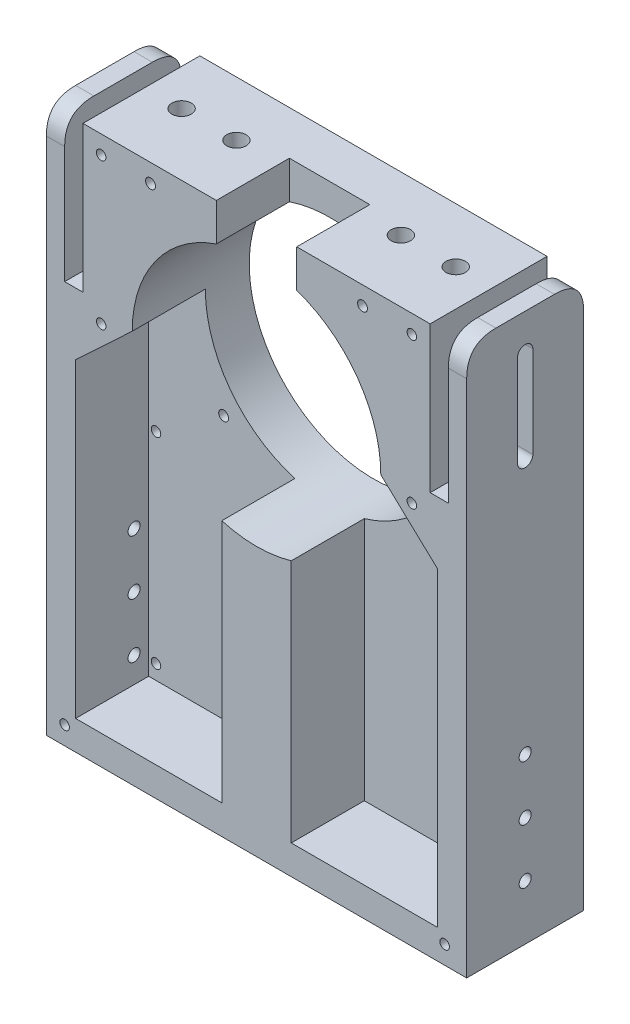
SolidWorks part; units mm, degrees
ref_plane "前基準面" through (0, 0, 0) normal (0, 0, 1) x (1, 0, 0)
ref_plane "上基準面" through (0, 0, 0) normal (0, 1, 0) x (1, 0, 0)
ref_plane "右基準面" through (0, 0, 0) normal (1, 0, 0) x (0, 0, -1)
sketch "草圖1" plane through (0, 0, 0) normal (0, 0, 1) x (1, 0, 0)
  line L1 (-57.5, -75) -> (57.5, -75)
  line L2 (-57.5, -75) -> (-57.5, 75)
  line L3 (-57.5, 75) -> (57.5, 75)
  line L4 (57.5, -75) -> (57.5, 75)
  line L5 (-57.5, -75) -> (57.5, 75) construction
  line L6 (-57.5, 75) -> (57.5, -75) construction
  point P0 (0, 0)
  dimension "D1" = 115
  dimension "D2" = 150
extrude "填料-伸長1" add sketch "草圖1" along normal blind 32
sketch "草圖2" plane through (0, 0, 32) normal (0, 0, 1) x (1, 0, 0)
  line L0 (57.5, 75) -> (-57.5, 75) construction
  circle A0 centre (0, 32.5) radius 34
  dimension "D1" = 68
  dimension "D2" = 42.5
extrude "除料-伸長1" cut sketch "草圖2" against normal through all
sketch "草圖3" plane through (0, 0, 32) normal (0, 0, 1) x (1, 0, 0)
  line L0 (-57.5, -75) -> (57.5, -75) construction
  line L1 (-49.5, -67) -> (-9.5, -67)
  line L2 (-49.5, -67) -> (-49.5, 18)
  line L3 (-49.5, 18) -> (-9.5, 18)
  line L4 (-9.5, -67) -> (-9.5, 18)
  line L5 (-49.5, -67) -> (-9.5, 18) construction
  line L6 (-49.5, 18) -> (-9.5, -67) construction
  line L7 (-57.5, 75) -> (-57.5, -75) construction
  point P0 (-29.5, -24.5)
  dimension "D1" = 8
  dimension "D2" = 8
  dimension "D3" = 40
  dimension "D4" = 85
extrude "除料-伸長2" cut sketch "草圖3" against normal blind 20
mirror "鏡射1" about plane through (0, 0, 0) normal (1, 0, 0) of "除料-伸長2"
hole_wizard "Ø1.0mm 定位孔1" [suppressed] positions "草圖4" profile "草圖5" hole size "Ø1.0" standard "ISO"
sketch "草圖4" plane through (0, 0, 0) normal (0, 0, -1) x (-1, 0, 0)
  line L0 (26.8701, 59.3701) -> (0, 32.5)
  line L1 (0, 32.5) -> (26.8701, 5.6299)
  line L3 (-26.8701, 59.3701) -> (0, 32.5)
  line L5 (-26.8701, 5.6299) -> (0, 32.5)
  line L7 (0, 32.5) -> (0, 70.5)
  circle A1 centre (0, 32.5) radius 38
  point P0 (26.8701, 59.3701)
  point P2 (-26.8701, 59.3701)
  point P4 (-26.8701, 5.6299)
  point P6 (26.8701, 5.6299)
  dimension "D1" = 76
  dimension "D2" = 45
  dimension "D3" = 90
  dimension "D4" = 45
  dimension "D5" = 90
sketch "草圖5" plane through (-26.8701, 59.3701, 0) normal (1, 0, 0) x (0, 1, 0)
  line L0 (0, 0) -> (0, 12.7801)
  line L1 (0, 12.7801) -> (1.3, 11.999)
  line L2 (1.3, 11.999) -> (1.3, 0.225)
  line L3 (1.3, 0.225) -> (1.525, 0)
  line L5 (1.525, 0) -> (0, 0)
  line L6 (-1.3, 0.225) -> (-1.525, 0) construction
  line L10 (0, 12.7801) -> (-1.3, 11.999) construction
  line L11 (0, -6.35) -> (0, 107.95) construction
  dimension "鑽孔直徑" = 2.6
  dimension "鑽孔深度" = 11.999
  dimension "近端錐孔直徑" = 3.05
  dimension "近端錐孔角度" = 90
  dimension "導頭角度" = 118
hole_wizard "Ø1.0mm 定位孔2" positions "草圖6" profile "草圖7" hole size "Ø1.0" standard "ISO"
sketch "草圖6" plane through (0, 0, 0) normal (0, 0, -1) x (-1, 0, 0)
  line L1 (-47.5, -8) -> (47.5, -8)
  line L2 (-47.5, -8) -> (-47.5, -63)
  line L3 (-47.5, -63) -> (47.5, -63)
  line L4 (47.5, -8) -> (47.5, -63)
  line L5 (-47.5, -8) -> (47.5, -63) construction
  line L6 (-47.5, -63) -> (47.5, -8) construction
  line L7 (57.5, 75) -> (57.5, -75) construction
  line L8 (57.5, -75) -> (-57.5, -75) construction
  point P0 (47.5, -8)
  point P2 (47.5, -63)
  point P4 (-47.5, -8)
  point P6 (-47.5, -63)
  dimension "D1" = 95
  dimension "D2" = 55
  dimension "D3" = 10
  dimension "D4" = 12
sketch "草圖7" plane through (-47.5, -8, 0) normal (1, 0, 0) x (0, 1, 0)
  line L0 (0, 0) -> (0, 12.7801)
  line L1 (0, 12.7801) -> (1.3, 11.999)
  line L2 (1.3, 11.999) -> (1.3, 0)
  line L5 (1.3, 0) -> (0, 0)
  line L10 (0, 12.7801) -> (-1.3, 11.999) construction
  line L11 (0, -6.35) -> (0, 107.95) construction
  dimension "鑽孔直徑" = 2.6
  dimension "鑽孔深度" = 11.999
  dimension "導頭角度" = 118
sketch "草圖8" plane through (0, 0, 32) normal (0, 0, 1) x (1, 0, 0)
  line L0 (57.5, 75) -> (-57.5, 75) construction
  line L1 (-47.5, 75) -> (-52.5, 75)
  line L2 (-47.5, 75) -> (-47.5, 35)
  line L3 (-47.5, 35) -> (-52.5, 35)
  line L4 (-52.5, 75) -> (-52.5, 35)
  line L5 (-57.5, 75) -> (-57.5, -75) construction
  dimension "D1" = 5
  dimension "D2" = 40
  dimension "D3" = 5
extrude "除料-伸長3" cut sketch "草圖8" against normal through all
mirror "鏡射2" about plane through (0, 0, 0) normal (1, 0, 0) of "除料-伸長3"
sketch "草圖9" plane through (0, 75, 0) normal (0, 1, 0) x (1, 0, 0)
  line L1 (11, -12) -> (-11, -12)
  line L2 (11, -12) -> (11, -32)
  line L3 (11, -32) -> (-11, -32)
  line L4 (-11, -12) -> (-11, -32)
  line L5 (0, 0) -> (0, -12) construction
  line L6 (47.5, -32) -> (-47.5, -32) construction
  dimension "D1" = 20
  dimension "D2" = 22
extrude "除料-伸長4" cut sketch "草圖9" against normal up to next
sketch "草圖11" plane through (57.5, 0, 0) normal (1, 0, 0) x (0, 0, -1)
  line L0 (-16, 75) -> (-16, 65) construction
  line L1 (-32, 75) -> (0, 75) construction
  line L2 (-13.9, 65) -> (-13.9, 40)
  line L3 (-18.1, 65) -> (-18.1, 40)
  arc A0 (-13.9, 65) -> (-18.1, 65) centre (-16, 65) ccw
  arc A1 (-18.1, 40) -> (-13.9, 40) centre (-16, 40) ccw
  dimension "D2" = 4.2
  dimension "D3" = 25
  dimension "D1" = 10
extrude "除料-伸長5" cut sketch "草圖11" against normal up to next
mirror "鏡射3" about plane through (0, 0, 0) normal (1, 0, 0) of "除料-伸長5"
fillet "圓角1" radius 8 4 edges at (-55, 75, 32) (-55, 75, 0) (55, 75, 0) (55, 75, 32) conic rho 0.5
hole_wizard "Ø1.0mm 定位孔4" positions "草圖12" profile "草圖13" hole size "Ø1.0" standard "ISO"
sketch "草圖12" plane through (0, 75, 0) normal (0, 1, 0) x (1, 0, 0)
  line L0 (47.5, 0) -> (-47.5, 0) construction
  line L3 (-47.5, 0) -> (-47.5, -32) construction
  point P0 (-37.5, -15)
  point P2 (-22.5, -15)
  dimension "D1" = 15
  dimension "D2" = 10
  dimension "D3" = 15
sketch "草圖13" plane through (-37.5, 75, 15) normal (1, 0, 0) x (0, 0, 1)
  line L0 (0, 0) -> (0, 16.5923)
  line L1 (0, 16.5923) -> (2.65, 15)
  line L2 (2.65, 15) -> (2.65, 0)
  line L5 (2.65, 0) -> (0, 0)
  line L10 (0, 16.5923) -> (-2.65, 15) construction
  line L11 (0, -6.35) -> (0, 107.95) construction
  dimension "鑽孔直徑" = 5.3
  dimension "鑽孔深度" = 15
  dimension "導頭角度" = 118
mirror "鏡射4" about plane through (0, 0, 0) normal (1, 0, 0) of "Ø1.0mm 定位孔4"
hole_wizard "Ø1.0mm 定位孔3" positions "草圖14" profile "草圖15" hole size "Ø1.0" standard "ISO"
sketch "草圖14" plane through (0, 0, 32) normal (0, 0, 1) x (1, 0, 0)
  line L0 (-57.5, -75) -> (57.5, -75) construction
  line L1 (-57.5, 67) -> (-57.5, -75) construction
  line L2 (-11, 75) -> (-47.5, 75) construction
  line L3 (-47.5, 35) -> (-47.5, 75) construction
  line L4 (47.5, 35) -> (47.5, 75) construction
  point P0 (-52.5, -70)
  point P2 (51.4647, -70)
  point P4 (-42.5, 70)
  point P6 (-42.5, 30)
  point P8 (42.5, 70)
  point P10 (42.5, 30)
  dimension "D1" = 5
  dimension "D2" = 5
  dimension "D3" = 5
  dimension "D4" = 5
  dimension "D5" = 5
  dimension "D6" = 40
sketch "草圖15" plane through (-52.5, -70, 32) normal (1, 0, 0) x (0, -1, 0)
  line L0 (0, 0) -> (0, 8.2811)
  line L1 (0, 8.2811) -> (1.3, 7.5)
  line L2 (1.3, 7.5) -> (1.3, 0)
  line L5 (1.3, 0) -> (0, 0)
  line L10 (0, 8.2811) -> (-1.3, 7.5) construction
  line L11 (0, -6.35) -> (0, 107.95) construction
  dimension "鑽孔直徑" = 2.6
  dimension "鑽孔深度" = 7.5
  dimension "導頭角度" = 118
sketch "草圖17" plane through (0, 0, 32) normal (0, 0, 1) x (1, 0, 0)
  line L0 (-49.5, 18) -> (-34, 32.5)
  line L1 (-49.5, 18) -> (-30.753, 18)
  line L2 (0, 32.5) -> (-34, 32.5) construction
  arc A0 (-11, 64.6714) -> (-30.753, 18) centre (0, 32.5) ccw construction
  arc A1 (-34, 32.5) -> (-30.753, 18) centre (0, 32.5) ccw
extrude "除料-伸長7" cut sketch "草圖17" against normal up to surface (20 mm away) up to face at (-48.8, -8, 12)
hole_wizard "Ø1.0mm 定位孔5" positions "草圖18" profile "草圖19" hole size "Ø1.0" standard "ISO" end condition up to next
sketch "草圖18" plane through (-57.5, 0, 0) normal (-1, 0, 0) x (0, 0, 1)
  line L0 (32, -75) -> (0, -75) construction
  line L1 (16, -60) -> (16, -75) construction
  point P0 (16, -60)
  point P2 (16, -45)
  point P4 (16, -30)
  dimension "D1" = 15
  dimension "D2" = 15
  dimension "D3" = 15
sketch "草圖19" plane through (-57.5, -60, 16) normal (0, 1, 0) x (0, 0, 1)
  line L0 (0, 0) -> (0, 67)
  line L1 (0, 67) -> (1.65, 67)
  line L2 (1.65, 67) -> (1.65, 0)
  line L5 (1.65, 0) -> (0, 0)
  line L11 (0, -6.35) -> (0, 107.95) construction
  dimension "貫穿孔直徑" = 3.3
  dimension "貫穿孔深度" = 67
mirror "鏡射5" about plane through (0, 0, 0) normal (1, 0, 0) of "Ø1.0mm 定位孔5"
mirror "鏡射6" about plane through (0, 0, 0) normal (1, 0, 0) of "除料-伸長7"
hole_wizard "Ø1.0mm 定位孔6" positions "草圖20" profile "草圖21" hole size "Ø1.0" standard "ISO" end condition through all
sketch "草圖20" plane through (0, 0, 0) normal (0, 0, -1) x (-1, 0, 0)
  line L0 (-47.5, 75) -> (47.5, 75) construction
  line L1 (-57.5, -75) -> (-57.5, 67) construction
  point P0 (-29, 70)
  point P2 (-29, 5)
  point P4 (29, 70)
  point P6 (29, 5)
  dimension "D1" = 5
  dimension "D2" = 28.5
  dimension "D3" = 58
  dimension "D4" = 65
sketch "草圖21" plane through (29, 70, 0) normal (1, 0, 0) x (0, 1, 0)
  line L0 (0, 0) -> (0, 32.04)
  line L1 (0, 32.04) -> (1.35, 32.04)
  line L2 (1.35, 32.04) -> (1.35, 0)
  line L5 (1.35, 0) -> (0, 0)
  line L11 (0, -6.35) -> (0, 107.95) construction
  dimension "貫穿孔直徑" = 2.7
  dimension "貫穿孔深度" = 32.04
